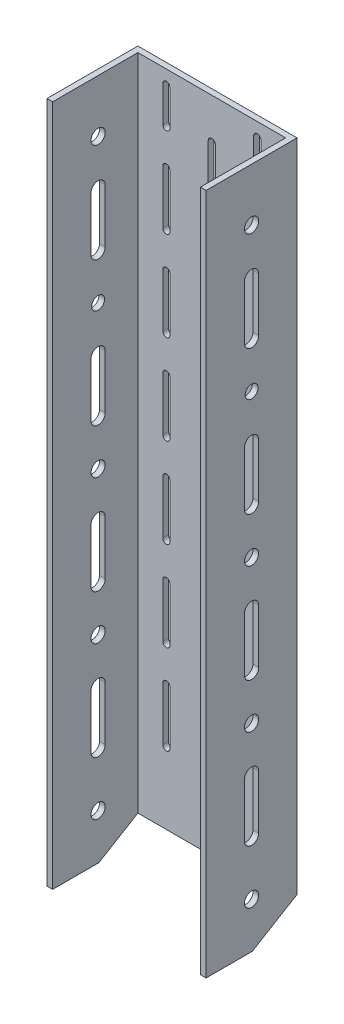
SolidWorks part; units mm, degrees
ref_plane "Front Plane" through (0, 0, 0) normal (0, 0, 1) x (1, 0, 0)
ref_plane "Top Plane" through (0, 0, 0) normal (0, 1, 0) x (1, 0, 0)
ref_plane "Right Plane" through (0, 0, 0) normal (1, 0, 0) x (0, 0, -1)
sketch "Sketch1" plane through (0, 0, 0) normal (0, 1, 0) x (1, 0, 0)
  line L0 (-41.275, 22.225) -> (-41.275, -25.4)
  line L1 (-44.45, 25.4) -> (44.45, 25.4)
  line L2 (-44.45, 25.4) -> (-44.45, -25.4)
  line L3 (-44.45, -25.4) -> (-41.275, -25.4)
  line L4 (44.45, 25.4) -> (44.45, -25.4)
  line L5 (-44.45, 25.4) -> (44.45, -25.4) construction
  line L6 (-44.45, -25.4) -> (44.45, 25.4) construction
  line L8 (41.275, 22.225) -> (41.275, -25.4)
  line L9 (-41.275, 22.225) -> (41.275, 22.225)
  line L10 (-41.275, -22.225) -> (41.275, -22.225) construction
  line L11 (-41.275, 22.225) -> (-41.275, -22.225) construction
  line L12 (41.275, 22.225) -> (41.275, -22.225) construction
  line L13 (41.275, -25.4) -> (44.45, -25.4)
  line L14 (-44.45, -25.4) -> (44.45, -25.4) construction
  point P0 (0, 0)
  dimension "D1" = 3.175
extrude "Boss-Extrude1" add sketch "Sketch1" along normal mid plane 381
sketch "Sketch3" plane through (44.45, 0, 0) normal (1, 0, 0) x (0, 0, -1)
  line L0 (-25.4, -190.5) -> (25.4, -190.5) construction
  circle A0 centre (0, -165.1) radius 3.9687
  dimension "D1" = 25.4
extrude "Cut-Extrude1" cut sketch "Sketch3" against normal blind 381
sketch "Sketch4" plane through (44.45, 0, 0) normal (1, 0, 0) x (0, 0, -1)
  line L0 (0, -135.1) -> (0, -105.1) construction
  line L1 (-3.9688, -135.1) -> (-3.9688, -105.1)
  line L2 (3.9688, -135.1) -> (3.9688, -105.1)
  line L3 (0, -54.85) -> (0, -24.85) construction
  line L4 (-3.9688, -54.85) -> (-3.9688, -24.85)
  line L5 (3.9688, -54.85) -> (3.9688, -24.85)
  line L6 (0, 25.4) -> (0, 55.4) construction
  line L7 (-3.9688, 25.4) -> (-3.9688, 55.4)
  line L8 (3.9688, 25.4) -> (3.9688, 55.4)
  line L9 (0, 105.65) -> (0, 135.65) construction
  line L10 (-3.9688, 105.65) -> (-3.9688, 135.65)
  line L11 (3.9688, 105.65) -> (3.9688, 135.65)
  arc A0 (-3.9688, -135.1) -> (3.9688, -135.1) centre (0, -135.1) ccw
  arc A1 (3.9688, -105.1) -> (-3.9688, -105.1) centre (0, -105.1) ccw
  arc A2 (-3.9688, -54.85) -> (3.9688, -54.85) centre (0, -54.85) ccw
  arc A3 (3.9688, -24.85) -> (-3.9688, -24.85) centre (0, -24.85) ccw
  circle A4 centre (0, -165.1) radius 3.9687 construction
  arc A5 (-3.9688, 25.4) -> (3.9688, 25.4) centre (0, 25.4) ccw
  arc A6 (3.9688, 55.4) -> (-3.9688, 55.4) centre (0, 55.4) ccw
  arc A7 (-3.9688, 105.65) -> (3.9688, 105.65) centre (0, 105.65) ccw
  arc A8 (3.9688, 135.65) -> (-3.9688, 135.65) centre (0, 135.65) ccw
  point P3 (0, -120.1)
  point P8 (0, -39.85)
  point P15 (0, 40.4)
  point P24 (0, 120.65)
  dimension "D1" = 30
  dimension "D3" = 50.25
  dimension "D4" = 30
  dimension "D6" = 30
  dimension "D2" = 30
  dimension "D5" = 50.25
  dimension "D7" = 50.25
extrude "Cut-Extrude2" cut sketch "Sketch4" against normal blind 381
sketch "Sketch5" plane through (44.45, 0, 0) normal (1, 0, 0) x (0, 0, -1)
  line L0 (0, -79.975) -> (16.8424, -79.975) construction
  line L1 (0, 0.275) -> (16.8424, 0.275) construction
  line L2 (0, 80.525) -> (16.8424, 80.525) construction
  line L3 (0, 161.05) -> (16.8424, 161.05) construction
  arc A0 (-3.9688, -54.85) -> (3.9687, -54.85) centre (0, -54.85) ccw construction
  arc A1 (3.9688, -105.1) -> (-3.9688, -105.1) centre (0, -105.1) ccw construction
  arc A2 (3.9688, -24.85) -> (-3.9688, -24.85) centre (0, -24.85) ccw construction
  arc A3 (3.9688, 55.4) -> (-3.9688, 55.4) centre (0, 55.4) ccw construction
  arc A4 (3.9688, 135.65) -> (-3.9688, 135.65) centre (0, 135.65) ccw construction
  circle A5 centre (0, 0.275) radius 3.9221
  circle A6 centre (0, -79.975) radius 3.9687
  circle A8 centre (0, 80.525) radius 3.5858
  circle A9 centre (0, 161.05) radius 3.9687
  dimension "D1" = 50.25
  dimension "D3" = 25.125
  dimension "D4" = 25.125
  dimension "D5" = 25.4
  dimension "D2" = 25.125
extrude "Cut-Extrude3" cut sketch "Sketch5" against normal blind 381
chamfer "Chamfer1" distance 25 distance2 15 1 edges at (0, -190.5, -25.4) first distance on face at (0, -190.5, 0.7937)
sketch "Sketch6" plane through (0, 0, -25.4) normal (0, 0, -1) x (-1, 0, 0)
  line L0 (0, -162.405) -> (0, -132.405) construction
  line L1 (-1.9844, -162.405) -> (-1.9844, -132.405)
  line L2 (1.9844, -162.405) -> (1.9844, -132.405)
  line L3 (41.275, -177.405) -> (-41.275, -177.405) construction
  line L4 (0, -112.405) -> (0, -82.405) construction
  line L5 (-1.9844, -112.405) -> (-1.9844, -82.405)
  line L6 (1.9844, -112.405) -> (1.9844, -82.405)
  line L7 (0, -62.405) -> (0, -32.405) construction
  line L8 (-1.9844, -62.405) -> (-1.9844, -32.405)
  line L9 (1.9844, -62.405) -> (1.9844, -32.405)
  line L10 (0, -12.405) -> (0, 17.595) construction
  line L11 (-2.3736, -12.405) -> (-2.3736, 17.595)
  line L12 (2.3736, -12.405) -> (2.3736, 17.595)
  line L13 (0, 37.595) -> (0, 67.595) construction
  line L14 (-1.9844, 37.595) -> (-1.9844, 67.595)
  line L15 (1.9844, 37.595) -> (1.9844, 67.595)
  line L16 (0, 87.595) -> (0, 117.595) construction
  line L17 (-1.9844, 87.595) -> (-1.9844, 117.595)
  line L18 (1.9844, 87.595) -> (1.9844, 117.595)
  line L19 (0, 137.595) -> (0, 167.595) construction
  line L20 (-1.9844, 137.595) -> (-1.9844, 167.595)
  line L21 (1.9844, 137.595) -> (1.9844, 167.595)
  line L22 (25.4, -137.405) -> (25.4, -107.405) construction
  line L23 (23.4156, -137.405) -> (23.4156, -107.405)
  line L24 (27.3844, -137.405) -> (27.3844, -107.405)
  line L25 (25.4, -87.405) -> (25.4, -57.405) construction
  line L26 (23.4156, -87.405) -> (23.4156, -57.405)
  line L27 (27.3844, -87.405) -> (27.3844, -57.405)
  line L28 (25.4, -37.405) -> (25.4, -7.405) construction
  line L29 (23.4156, -37.405) -> (23.4156, -7.405)
  line L30 (27.3844, -37.405) -> (27.3844, -7.405)
  line L31 (25.4, 12.595) -> (25.4, 42.595) construction
  line L32 (23.4156, 12.595) -> (23.4156, 42.595)
  line L33 (27.3844, 12.595) -> (27.3844, 42.595)
  line L34 (25.4, 62.595) -> (25.4, 92.595) construction
  line L35 (23.4156, 62.595) -> (23.4156, 92.595)
  line L36 (27.3844, 62.595) -> (27.3844, 92.595)
  line L37 (25.4, 112.595) -> (25.4, 142.595) construction
  line L38 (23.4156, 112.595) -> (23.4156, 142.595)
  line L39 (27.3844, 112.595) -> (27.3844, 142.595)
  line L40 (25.4, 162.595) -> (25.4, 182.595) construction
  line L41 (23.4156, 162.595) -> (23.4156, 182.595)
  line L42 (27.3844, 162.595) -> (27.3844, 182.595)
  line L43 (0, -175.5) -> (0, -168.831) construction
  line L44 (-44.45, -175.5) -> (44.45, -175.5) construction
  line L45 (-25.4, -137.405) -> (-25.4, -107.405) construction
  line L46 (-23.4156, -137.405) -> (-23.4156, -107.405)
  line L47 (-27.3844, -137.405) -> (-27.3844, -107.405)
  line L48 (-25.4, -87.405) -> (-25.4, -57.405) construction
  line L49 (-23.4156, -87.405) -> (-23.4156, -57.405)
  line L50 (-27.3844, -87.405) -> (-27.3844, -57.405)
  line L51 (-25.4, -37.405) -> (-25.4, -7.405) construction
  line L52 (-23.4156, -37.405) -> (-23.4156, -7.405)
  line L53 (-27.3844, -37.405) -> (-27.3844, -7.405)
  line L54 (-25.4, 12.595) -> (-25.4, 42.595) construction
  line L55 (-23.4156, 12.595) -> (-23.4156, 42.595)
  line L56 (-27.3844, 12.595) -> (-27.3844, 42.595)
  line L57 (-25.4, 62.595) -> (-25.4, 92.595) construction
  line L58 (-23.4156, 62.595) -> (-23.4156, 92.595)
  line L59 (-27.3844, 62.595) -> (-27.3844, 92.595)
  line L60 (-25.4, 112.595) -> (-25.4, 142.595) construction
  line L61 (-23.4156, 112.595) -> (-23.4156, 142.595)
  line L62 (-27.3844, 112.595) -> (-27.3844, 142.595)
  line L63 (-25.4, 162.595) -> (-25.4, 182.595) construction
  line L64 (-23.4156, 162.595) -> (-23.4156, 182.595)
  line L65 (-27.3844, 162.595) -> (-27.3844, 182.595)
  arc A0 (-1.9844, -162.405) -> (1.9844, -162.405) centre (0, -162.405) ccw
  arc A1 (1.9844, -132.405) -> (-1.9844, -132.405) centre (0, -132.405) ccw
  arc A2 (-1.9844, -112.405) -> (1.9844, -112.405) centre (0, -112.405) ccw
  arc A3 (1.9844, -82.405) -> (-1.9844, -82.405) centre (0, -82.405) ccw
  arc A4 (-1.9844, -62.405) -> (1.9844, -62.405) centre (0, -62.405) ccw
  arc A5 (1.9844, -32.405) -> (-1.9844, -32.405) centre (0, -32.405) ccw
  arc A6 (-2.3736, -12.405) -> (2.3736, -12.405) centre (0, -12.405) ccw
  arc A7 (2.3736, 17.595) -> (-2.3736, 17.595) centre (0, 17.595) ccw
  arc A8 (-1.9844, 37.595) -> (1.9844, 37.595) centre (0, 37.595) ccw
  arc A9 (1.9844, 67.595) -> (-1.9844, 67.595) centre (0, 67.595) ccw
  arc A10 (-1.9844, 87.595) -> (1.9844, 87.595) centre (0, 87.595) ccw
  arc A11 (1.9844, 117.595) -> (-1.9844, 117.595) centre (0, 117.595) ccw
  arc A12 (-1.9844, 137.595) -> (1.9844, 137.595) centre (0, 137.595) ccw
  arc A13 (1.9844, 167.595) -> (-1.9844, 167.595) centre (0, 167.595) ccw
  arc A14 (23.4156, -137.405) -> (27.3844, -137.405) centre (25.4, -137.405) ccw
  arc A15 (27.3844, -107.405) -> (23.4156, -107.405) centre (25.4, -107.405) ccw
  arc A16 (23.4156, -87.405) -> (27.3844, -87.405) centre (25.4, -87.405) ccw
  arc A17 (27.3844, -57.405) -> (23.4156, -57.405) centre (25.4, -57.405) ccw
  arc A18 (23.4156, -37.405) -> (27.3844, -37.405) centre (25.4, -37.405) ccw
  arc A19 (27.3844, -7.405) -> (23.4156, -7.405) centre (25.4, -7.405) ccw
  arc A20 (23.4156, 12.595) -> (27.3844, 12.595) centre (25.4, 12.595) ccw
  arc A21 (27.3844, 42.595) -> (23.4156, 42.595) centre (25.4, 42.595) ccw
  arc A22 (23.4156, 62.595) -> (27.3844, 62.595) centre (25.4, 62.595) ccw
  arc A23 (27.3844, 92.595) -> (23.4156, 92.595) centre (25.4, 92.595) ccw
  arc A24 (23.4156, 112.595) -> (27.3844, 112.595) centre (25.4, 112.595) ccw
  arc A25 (27.3844, 142.595) -> (23.4156, 142.595) centre (25.4, 142.595) ccw
  arc A26 (23.4156, 162.595) -> (27.3844, 162.595) centre (25.4, 162.595) ccw
  arc A27 (27.3844, 182.595) -> (23.4156, 182.595) centre (25.4, 182.595) ccw
  arc A28 (-23.4156, -137.405) -> (-27.3844, -137.405) centre (-25.4, -137.405) cw
  arc A29 (-27.3844, -107.405) -> (-23.4156, -107.405) centre (-25.4, -107.405) cw
  arc A30 (-23.4156, -87.405) -> (-27.3844, -87.405) centre (-25.4, -87.405) cw
  arc A31 (-27.3844, -57.405) -> (-23.4156, -57.405) centre (-25.4, -57.405) cw
  arc A32 (-23.4156, -37.405) -> (-27.3844, -37.405) centre (-25.4, -37.405) cw
  arc A33 (-27.3844, -7.405) -> (-23.4156, -7.405) centre (-25.4, -7.405) cw
  arc A34 (-23.4156, 12.595) -> (-27.3844, 12.595) centre (-25.4, 12.595) cw
  arc A35 (-27.3844, 42.595) -> (-23.4156, 42.595) centre (-25.4, 42.595) cw
  arc A36 (-23.4156, 62.595) -> (-27.3844, 62.595) centre (-25.4, 62.595) cw
  arc A37 (-27.3844, 92.595) -> (-23.4156, 92.595) centre (-25.4, 92.595) cw
  arc A38 (-23.4156, 112.595) -> (-27.3844, 112.595) centre (-25.4, 112.595) cw
  arc A39 (-27.3844, 142.595) -> (-23.4156, 142.595) centre (-25.4, 142.595) cw
  arc A40 (-23.4156, 162.595) -> (-27.3844, 162.595) centre (-25.4, 162.595) cw
  arc A41 (-27.3844, 182.595) -> (-23.4156, 182.595) centre (-25.4, 182.595) cw
  point P3 (0, -147.405)
  point P12 (0, -97.405)
  point P19 (0, -47.405)
  point P26 (0, 2.595)
  point P31 (0, 52.595)
  point P40 (0, 102.595)
  point P47 (0, 152.595)
  point P54 (25.4, -122.405)
  point P61 (25.4, -72.405)
  point P68 (25.4, -22.405)
  point P75 (25.4, 27.595)
  point P82 (25.4, 77.595)
  point P89 (25.4, 127.595)
  point P96 (25.4, 172.595)
  point P107 (-25.4, -122.405)
  point P114 (-25.4, -72.405)
  point P121 (-25.4, -22.405)
  point P128 (-25.4, 27.595)
  point P135 (-25.4, 77.595)
  point P142 (-25.4, 127.595)
  point P149 (-25.4, 172.595)
  dimension "D1" = 30
  dimension "D3" = 30
  dimension "D5" = 30
  dimension "D9" = 30
  dimension "D11" = 30
  dimension "D13" = 30
  dimension "D15" = 30
  dimension "D17" = 20
  dimension "D19" = 30
  dimension "D21" = 30
  dimension "D23" = 20
  dimension "D25" = 30
  dimension "D27" = 20
  dimension "D2" = 15
  dimension "D4" = 20
  dimension "D6" = 20
  dimension "D7" = 20
  dimension "D8" = 30
  dimension "D10" = 20
  dimension "D12" = 20
  dimension "D14" = 20
  dimension "D16" = 40
  dimension "D18" = 30
  dimension "D20" = 20
  dimension "D22" = 20
  dimension "D24" = 30
  dimension "D26" = 20
  dimension "D28" = 20
  dimension "D29" = 25.4
extrude "Cut-Extrude4" cut sketch "Sketch6" against normal blind 10
